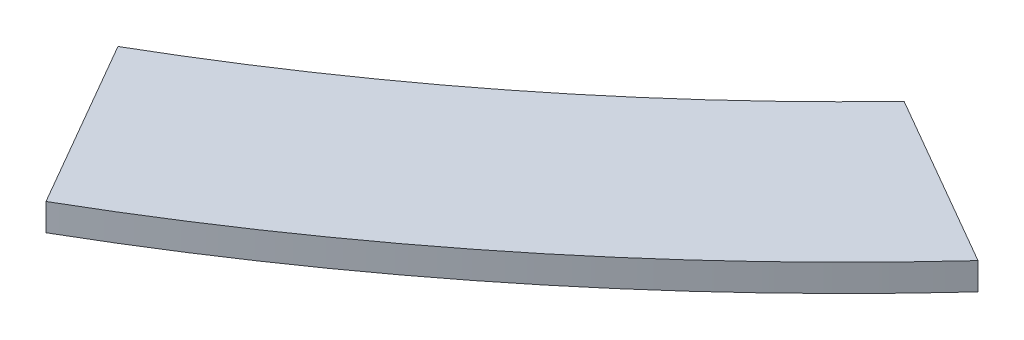
SolidWorks part; units mm, degrees
material "PTFE (general)"
ref_plane "Front Plane" through (0, 0, 0) normal (0, 0, 1) x (1, 0, 0)
ref_plane "Top Plane" through (0, 0, 0) normal (0, 1, 0) x (1, 0, 0)
ref_plane "Right Plane" through (0, 0, 0) normal (1, 0, 0) x (0, 0, -1)
sketch "Sketch1" plane through (0, 0, 0) normal (0, 1, 0) x (1, 0, 0)
  line L0 (-13.335, -54.2656) -> (-13.335, -59.9391)
  line L1 (13.335, -54.2656) -> (13.335, -59.9391)
  line L2 (0, 0) -> (53.1779, -30.7022)
  line L3 (40.3279, -38.6812) -> (45.2412, -41.518)
  line L4 (0, 0) -> (41.2834, -71.505)
  line L5 (0, 0) -> (-69.401, -7.9072) construction
  line L6 (0, 0) -> (0, -23.1086) construction
  line L7 (13.335, -59.9391) -> (45.2412, -41.518) construction
  circle A0 centre (0, 0) radius 55.88
  circle A1 centre (0, 0) radius 76.2
  circle A2 centre (0, 0) radius 59.69
  circle A5 centre (0, 0) radius 61.4045
  dimension "D1" = 111.76
  dimension "D2" = 152.4
  dimension "D4" = 13.335
  dimension "D5" = 13.335
  dimension "D9" = 69.85
  dimension "D10" = 83.5
  dimension "D7" = 5.5245
  dimension "D6" = 60
  dimension "D8" = 13.335
  dimension "D11" = 36.8422
  dimension "D12" = 18.4211
  dimension "D3" = 3.81
extrude "Boss-Extrude1" add sketch "Sketch1" along normal blind 0.762 contours L4 A2 L3 A0 | L4 A5 L3 A2 region at (35.7374, 0, 45.1975) region at (37.6678, 0, 47.1196)
equation "\"Middle Coupler Inner Daimeter\"= 3.875in"
equation "\"Middle Coupler  Wall Thickness\" = 0.25in"
equation "\"Middle Coupler Bottom Thickness\"= 0.2in"
equation "\"Bearing Rail Offset\"= 0.45in"
equation "\"3-56 UNF Tap\"= 0.089in"
equation "\"3-56 UNF Clearance\"= 0.104in"
equation "\"Ball Bearing Distance\"= 0.03in"
equation "\"D1@Sketch1\"=\"Middle Coupler Inner Daimeter\"+0.5+0.0125*2in"
equation "\"TCA Outer Diameter\" = 6in"
equation "\"D2@Sketch1\"=\"TCA Outer Diameter\""
equation "\"D4@Sketch1\"=0.50 + (0.05/2)"
equation "\"D5@Sketch1\"=\"D4@Sketch1\""
equation "\"Interstage Aeroframe Wall Thickness\" = 0.072in"
equation "\"Compression Spring OD\"= 0.42in"
equation "\"10-24 Tap\"= 0.157in"
equation "\"10-24 Clearance\"= 0.196in"
equation "\"D3@Sketch1\"=0.125in+(0.05/2)"
equation "\"Lower Stage Fuselage Wall Thickness\" = 0.25in"
equation "\"6-32 Tap\" = 0.107in"
equation "\"1/4-20 Tap\" = 0.201in"
equation "\"3-48 Tap\"= 0.079in"
equation "\"12-24 Tap\" = 0.177in"
equation "\"3-48 Clearance\" = 0.104in"
equation "\"6-32 Clearance\" = 0.144"
equation "\"D9@Sketch1\"=(\"D2@Sketch1\"-0.5)/2"
equation "\"D1@Boss-Extrude1\"=3/16"
equation "\"D7@Sketch1\"=3/16 + 0.03"
equation "\"D8@Sketch1\"=\"D4@Sketch1\""
equation "\"D12@Sketch1\"=\"D11@Sketch1\"/2"
